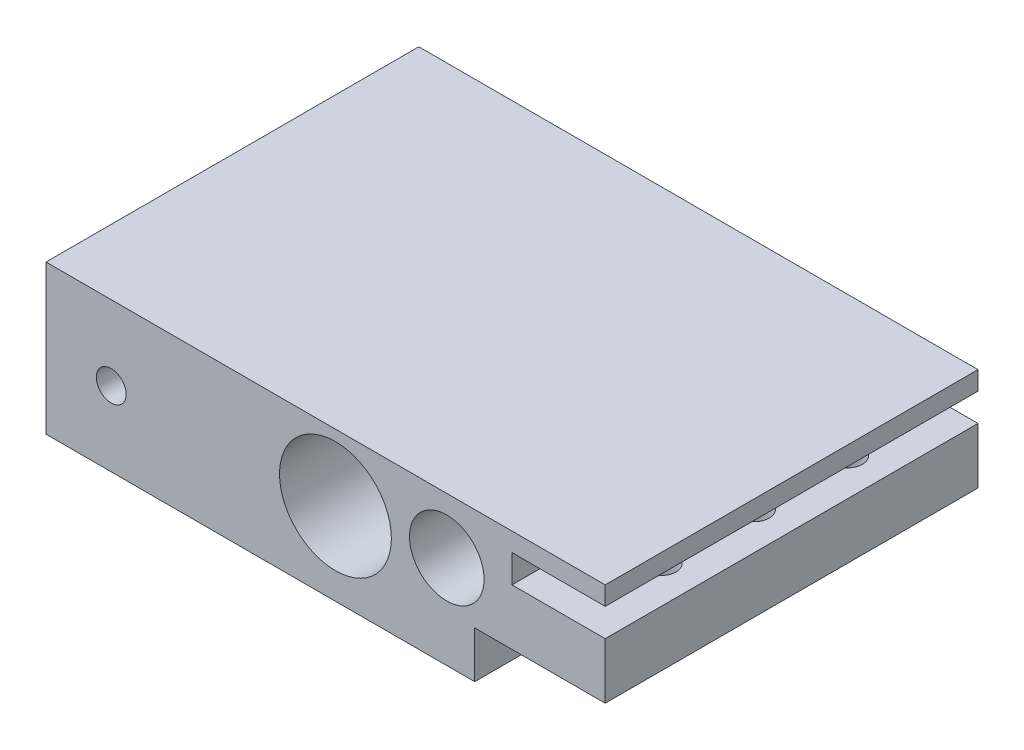
SolidWorks part; units mm, degrees
ref_plane "Front Plane" through (0, 0, 0) normal (0, 0, 1) x (1, 0, 0)
ref_plane "Top Plane" through (0, 0, 0) normal (0, 1, 0) x (1, 0, 0)
ref_plane "Right Plane" through (0, 0, 0) normal (1, 0, 0) x (0, 0, -1)
sketch "Sketch1" plane through (0, 0, 0) normal (0, 0, 1) x (1, 0, 0)
  line L0 (20.6606, -2.989) -> (20.6606, -5.989)
  line L1 (-9.3394, -0.489) -> (20.6606, -0.489)
  line L2 (-9.3394, -0.489) -> (-9.3394, -2.7427)
  line L4 (20.6606, -0.489) -> (20.6606, -1.489)
  line L5 (20.6606, -1.489) -> (15.6606, -1.489)
  line L7 (20.6606, -2.989) -> (15.6606, -2.989)
  line L8 (15.6606, -1.489) -> (15.6606, -2.989)
  line L9 (13.6606, -5.989) -> (20.6606, -5.989)
  line L11 (-9.3394, -2.7427) -> (-9.3394, -8.489)
  line L12 (-9.3394, -8.489) -> (13.6606, -8.489)
  line L13 (13.6606, -5.989) -> (13.6606, -8.489)
  circle A0 centre (6.1885, -4.0666) radius 3
  circle A1 centre (12.1606, -3.489) radius 2
  dimension "D6" = 6
  dimension "D7" = 4
  dimension "D11" = 3
  dimension "D13" = 3.5776
  dimension "D1" = 5
  dimension "D2" = 1
  dimension "D3" = 8
  dimension "D4" = 1.5
  dimension "D5" = 30
  dimension "D8" = 2
  dimension "D9" = 3
  dimension "D10" = 1.5
  dimension "D12" = 6
extrude "Boss-Extrude1" add sketch "Sketch1" along normal blind 20
sketch "Sketch2" plane through (-9.3394, 0, 0) normal (-1, 0, 0) x (0, 0, 1)
  line L0 (0, -0.489) -> (0, -8.489) construction
  line L1 (20, -0.489) -> (20, -8.489) construction
  circle A0 centre (6, -4.489) radius 3
  circle A1 centre (14, -4.489) radius 3
  point P6 (0, -4.489)
  dimension "D1" = 6
  dimension "D2" = 6
  dimension "D3" = 6
  dimension "D4" = 6
extrude "Cut-Extrude1" cut sketch "Sketch2" against normal blind 7
ref_axis "Axis1" through (12.1606, -3.489, 20) along (0, 0, -1)
ref_axis "Axis2" through (6.1885, -4.0666, 20) along (0, 0, -1)
ref_axis "Axis3" through (-2.3394, -4.489, 6) along (-1, 0, 0)
ref_axis "Axis4" through (-2.3394, -4.489, 14) along (-1, 0, 0)
hole_wizard "M2x0.4 Tapped Hole1" positions "Sketch3" profile "Sketch4" tap size "M2x0.4" standard "BSI" end condition up to next
sketch "Sketch3" plane through (0, -8.489, 0) normal (0, -1, 0) x (-1, 0, 0)
  line L0 (-12.1606, -20) -> (-12.1606, 0) construction
  line L1 (-6.1885, -20) -> (-6.1885, 0) construction
  line L2 (-13.6606, -20) -> (-13.6606, 0) construction
  point P0 (-12.1606, -10)
  point P2 (-6.1885, -10)
  point P13 (-13.6606, -10)
sketch "Sketch4" plane through (12.1606, -8.489, 10) normal (1, 0, 0) x (0, 0, -1)
  line L0 (0, 0) -> (0, 3)
  line L1 (0, 3) -> (0.8, 3)
  line L2 (0.8, 3) -> (0.8, 0)
  line L5 (0.8, 0) -> (0, 0)
  line L11 (0, -6.35) -> (0, 107.95) construction
  dimension "Thru Tap Drill Dia." = 1.6
  dimension "Thru Tap Drill Depth" = 3
cosmetic thread "Hole Thread1"
cosmetic thread "Hole Thread2"
hole_wizard "M2x0.4 Tapped Hole2" positions "Sketch5" profile "Sketch6" tap size "M2x0.4" standard "BSI" end condition up to next
sketch "Sketch5" plane through (0, 0, 0) normal (0, 0, -1) x (-1, 0, 0)
  line L0 (2.3394, -4.489) -> (9.3394, -4.489) construction
  line L2 (9.3394, -0.489) -> (9.3394, -8.489) construction
  point P0 (5.8394, -4.489)
  dimension "D1" = 3.5
sketch "Sketch6" plane through (-5.8394, -4.489, 0) normal (1, 0, 0) x (0, 1, 0)
  line L0 (0, 0) -> (0, 3)
  line L1 (0, 3) -> (0.8, 3)
  line L2 (0.8, 3) -> (0.8, 0)
  line L5 (0.8, 0) -> (0, 0)
  line L11 (0, -6.35) -> (0, 107.95) construction
  dimension "Thru Tap Drill Dia." = 1.6
  dimension "Thru Tap Drill Depth" = 3
cosmetic thread "Hole Thread3"
ref_plane "Plane1" through (0, 0, 10) normal (0, 0, -1) x (-1, 0, 0)
mirror "Mirror1" about plane through (0, 0, 10) normal (0, 0, -1) of "M2x0.4 Tapped Hole2"
cosmetic thread "Hole Thread4"
hole_wizard "M2x0.4 Tapped Hole3" positions "Sketch7" profile "Sketch8" tap size "M2x0.4" standard "BSI" end condition up to next
sketch "Sketch7" plane through (0, -5.989, 0) normal (0, -1, 0) x (-1, 0, 0)
  line L0 (4.4, -10) -> (-4.4, -10) construction
  line L1 (-20.6606, -20) -> (-20.6606, 0) construction
  point P0 (-18.6606, -5)
  point P5 (-18.6606, -15)
  point P6 (-18.6606, -10)
  dimension "D1" = 2
  dimension "D2" = 5
sketch "Sketch8" plane through (18.6606, -5.989, 5) normal (1, 0, 0) x (0, 0, -1)
  line L0 (0, 0) -> (0, 3)
  line L1 (0, 3) -> (0.8, 3)
  line L2 (0.8, 3) -> (0.8, 0)
  line L5 (0.8, 0) -> (0, 0)
  line L11 (0, -6.35) -> (0, 107.95) construction
  dimension "Thru Tap Drill Dia." = 1.6
  dimension "Thru Tap Drill Depth" = 3
cosmetic thread "Hole Thread5"
cosmetic thread "Hole Thread6"
cosmetic thread "Hole Thread7"
